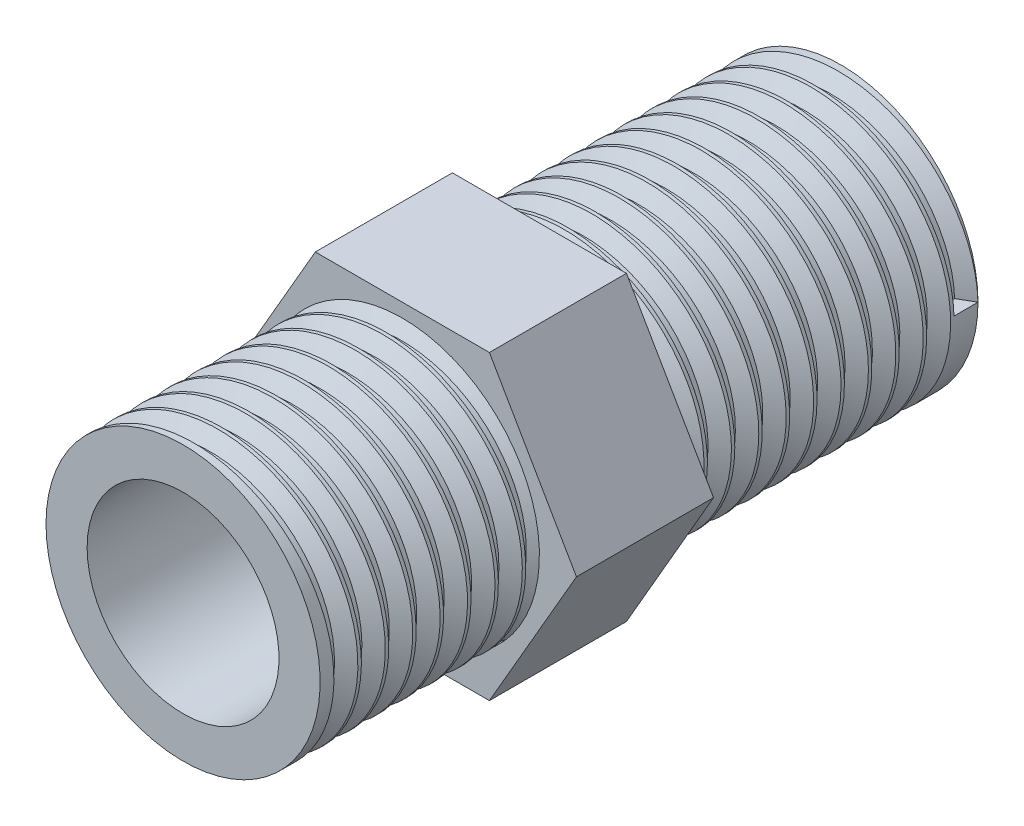
SolidWorks part; units mm, degrees
ref_plane "Front Plane" through (0, 0, 0) normal (0, 0, 1) x (1, 0, 0)
ref_plane "Top Plane" through (0, 0, 0) normal (0, 1, 0) x (1, 0, 0)
ref_plane "Right Plane" through (0, 0, 0) normal (1, 0, 0) x (0, 0, -1)
sketch "Sketch5" plane through (0, 0, 0) normal (0, 0, 1) x (1, 0, 0)
  line L1 (6.3509, 0) -> (3.1754, 5.5)
  line L2 (3.1754, 5.5) -> (-3.1754, 5.5)
  line L3 (-3.1754, 5.5) -> (-6.3509, 0)
  line L4 (-6.3509, 0) -> (-3.1754, -5.5)
  line L5 (-3.1754, -5.5) -> (3.1754, -5.5)
  line L6 (3.1754, -5.5) -> (6.3509, 0)
  circle A0 centre (0, 0) radius 5.5 construction
  dimension "D1" = 11
extrude "Boss-Extrude1" add sketch "Sketch5" along normal blind 5
sketch "Sketch6" plane through (0, 0, 5) normal (0, 0, 1) x (1, 0, 0)
  circle A0 centre (0, 0) radius 5
  dimension "D1" = 10
extrude "Boss-Extrude2" add sketch "Sketch6" along normal blind 8
sketch "Sketch7" plane through (0, 0, 0) normal (0, 0, -1) x (-1, 0, 0)
  circle A0 centre (0, 0) radius 5
  dimension "D1" = 10
extrude "Boss-Extrude3" add sketch "Sketch7" along normal blind 11
sketch "Sketch8" plane through (0, 0, -11) normal (0, 0, -1) x (-1, 0, 0)
  circle A0 centre (0, 0) radius 3.5
  dimension "D1" = 7
extrude "Cut-Extrude2" cut sketch "Sketch8" against normal through all
thread "Thread1" pitch 1 method cut profile "Thread Profile2" start angle 0, offset 0, length 8, pitch 1, diameter 10
ref_plane "Plane2" through (-5, 0, 13) normal (0, -1, 0) x (-1, 0, 0)
sketch "Thread Profile2" plane through (-5, 0, 13) normal (0, -1, 0) x (-1, 0, 0)
  line L0 (0, 0) -> (0, 1) construction
  line L11 (0, 0) -> (0, 0.875)
  line L12 (0, 0.875) -> (-0.5413, 0.5625)
  line L13 (-0.5413, 0.5625) -> (-0.5413, 0.3125)
  line L15 (-0.5413, 0.3125) -> (0, 0)
  line L17 (-0.5413, 0.4375) -> (0, 0.4375) construction
  point P2 (0, 0)
  dimension "Pitch" = 1
  dimension "Profile_Angle" = 60
  dimension "Profile_Land" = 0.25
  dimension "Profile_Height" = 0.5413
thread "Thread2" pitch 1 method cut profile "Thread Profile3" start angle 0, offset 0, length 11, pitch 1, diameter 10
ref_plane "Plane3" through (5, 0, -11) normal (0, -1, 0) x (1, 0, 0)
sketch "Thread Profile3" plane through (5, 0, -11) normal (0, -1, 0) x (1, 0, 0)
  line L0 (0, 0) -> (0, 1) construction
  line L11 (0, 0) -> (0, 0.875)
  line L12 (0, 0.875) -> (-0.5413, 0.5625)
  line L13 (-0.5413, 0.5625) -> (-0.5413, 0.3125)
  line L15 (-0.5413, 0.3125) -> (0, 0)
  line L17 (-0.5413, 0.4375) -> (0, 0.4375) construction
  point P2 (0, 0)
  dimension "Pitch" = 1
  dimension "Profile_Angle" = 60
  dimension "Profile_Land" = 0.25
  dimension "Profile_Height" = 0.5413
